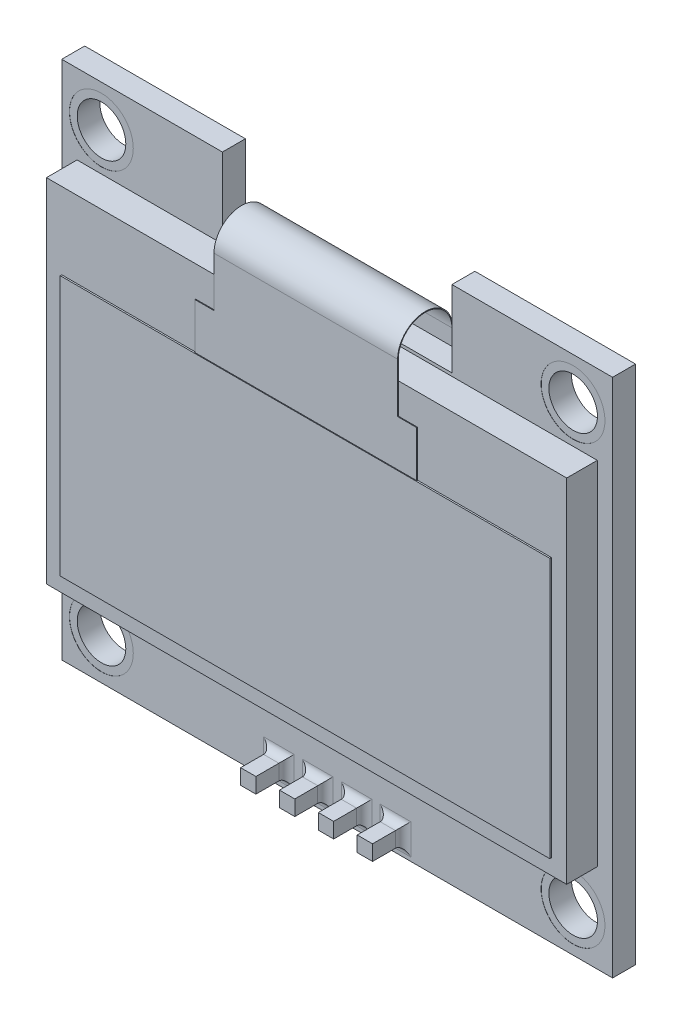
SolidWorks part; units mm, degrees
ref_plane "Alzado" through (0, 0, 0) normal (0, 0, 1) x (1, 0, 0)
ref_plane "Planta" through (0, 0, 0) normal (0, 1, 0) x (1, 0, 0)
ref_plane "Vista lateral" through (0, 0, 0) normal (1, 0, 0) x (0, 0, -1)
sketch "Croquis1" plane through (0, 0, 0) normal (0, 0, 1) x (1, 0, 0)
  line L1 (-18, 17) -> (18, 17)
  line L2 (-18, 17) -> (-18, -17)
  line L3 (-18, -17) -> (18, -17)
  line L4 (18, 17) -> (18, -17)
  line L5 (-18, 17) -> (18, -17) construction
  line L6 (-18, -17) -> (18, 17) construction
  point P0 (0, 0)
  dimension "D1" = 36
  dimension "D2" = 34
extrude "Saliente-Extruir1" add sketch "Croquis1" along normal blind 1.5
sketch "Croquis2" plane through (0, 0, 1.5) normal (0, 0, 1) x (1, 0, 0)
  line L0 (18, 17) -> (-18, 17) construction
  line L1 (-7.5, 17) -> (7.5, 17)
  line L2 (-7.5, 17) -> (-7.5, 12)
  line L3 (-7.5, 12) -> (7.5, 12)
  line L4 (7.5, 17) -> (7.5, 12)
  point P6 (0, 12)
  point P7 (0, 17)
  dimension "D1" = 15
  dimension "D2" = 5
extrude "Cortar-Extruir1" cut sketch "Croquis2" against normal blind 1.5
sketch "Croquis3" plane through (0, 0, 1.5) normal (0, 0, 1) x (1, 0, 0)
  line L0 (15.4125, 14.2875) -> (15.4125, -14.2875) construction
  line L1 (18, -17) -> (18, 17) construction
  line L2 (-15.4125, -14.2875) -> (15.4125, -14.2875) construction
  line L3 (-18, -17) -> (18, -17) construction
  circle A0 centre (-15.4125, 14.2875) radius 1.5875
  circle A1 centre (15.4125, 14.2875) radius 1.5875
  circle A2 centre (15.4125, -14.2875) radius 1.5875
  circle A3 centre (-15.4125, -14.2875) radius 1.5875
  point P8 (15.4125, 15.875)
  point P9 (17, 14.2875)
  point P10 (15.4125, -15.875)
  point P11 (-17, 14.2875)
  point P12 (15.4125, 0)
  point P13 (18, 0)
  point P14 (0, -14.2875)
  point P17 (0, -17)
  dimension "D1" = 3.175
  dimension "D2" = 31.75
  dimension "D3" = 34
extrude "Cortar-Extruir2" cut sketch "Croquis3" against normal blind 2.54
sketch "Croquis4" plane through (0, 0, 1.5) normal (0, 0, 1) x (1, 0, 0)
  line L0 (-18, -17) -> (18, -17) construction
  line L1 (-17, 11.8) -> (17, 11.8)
  line L2 (-17, 11.8) -> (-17, -11.2)
  line L3 (-17, -11.2) -> (17, -11.2)
  line L4 (17, 11.8) -> (17, -11.2)
  point P6 (0, -11.2)
  dimension "D1" = 34
  dimension "D2" = 23
  dimension "D3" = 5.8
extrude "Saliente-Extruir2" add sketch "Croquis4" along normal blind 2
sketch "Croquis5" plane through (0, 0, 3.5) normal (0, 0, 1) x (1, 0, 0)
  line L0 (-17, -11.2) -> (17, -11.2) construction
  line L1 (16, -10.2) -> (-16, -10.2)
  line L2 (16, -10.2) -> (16, 6.8)
  line L3 (16, 6.8) -> (-16, 6.8)
  line L4 (-16, -10.2) -> (-16, 6.8)
  line L5 (17, -11.2) -> (17, 11.8) construction
  line L6 (-17, 11.8) -> (-17, -11.2) construction
  line L7 (17, 11.8) -> (-17, 11.8) construction
  dimension "D1" = 1
  dimension "D2" = 1
  dimension "D3" = 1
  dimension "D4" = 5
sketch "Croquis7" plane through (0, 0, 0) normal (0, 0, -1) x (-1, 0, 0)
  line L0 (-11, 6) -> (11, 6)
  line L1 (-11, 6) -> (-11, 9)
  line L2 (-11, 9) -> (11, 9) construction
  line L3 (11, 9) -> (11, 6)
  line L4 (7.5, 12) -> (-7.5, 12) construction
  line L5 (-11, 9) -> (-6, 12.5)
  line L6 (-6, 12.5) -> (-6, 13)
  line L7 (-6, 13) -> (6, 13)
  line L8 (6, 13) -> (6, 12.5)
  line L9 (6, 12.5) -> (11, 9)
  point P3 (0, 6)
  point P7 (0, 13)
  dimension "D1" = 22
  dimension "D2" = 3
  dimension "D3" = 6
  dimension "D4" = 3.5
  dimension "D6" = 12
  dimension "D7" = 0.5
extrude "Saliente-Extruir3" add sketch "Croquis7" along normal blind 0.05
sketch "Croquis8" plane through (0, 0, 0) normal (1, 0, 0) x (0, 0, -1)
  line L0 (-3.5, 11.8) -> (-3.55, 11.8) construction
  line L1 (0.025, 13) -> (0.025, 13.0479)
  line L2 (0.05, 13) -> (0, 13) construction
  line L3 (-3.525, 13.0479) -> (-3.525, 11.8)
  arc A0 (0.025, 13.0479) -> (-3.525, 13.0479) centre (-1.75, 13.0479) ccw
  point P3 (-3.525, 11.8)
  dimension "D1" = 0.05
sketch "Croquis12" plane through (0, 13, 0) normal (0, 1, 0) x (1, 0, 0)
  line L1 (6, 0) -> (-6, 0)
  line L2 (6, 0) -> (6, 0.05)
  line L3 (6, 0.05) -> (-6, 0.05)
  line L4 (-6, 0) -> (-6, 0.05)
extrude "Saliente-Extruir5" add sketch "Croquis5" along normal blind 0.1
sketch "Croquis14" plane through (0, 0, 3.5) normal (0, 0, 1) x (1, 0, 0)
  line L0 (17, 11.8) -> (-17, 11.8) construction
  line L1 (16, 6.8) -> (-16, 6.8) construction
  line L2 (-6, 11.8) -> (6, 11.8)
  line L3 (-6, 11.8) -> (-6, 9.8)
  line L5 (6, 11.8) -> (6, 9.8)
  line L6 (-7.2481, 3.8) -> (7.2481, 3.8)
  line L7 (-7.2481, 3.8) -> (-7.2481, 9.8)
  line L8 (-7.2481, 9.8) -> (-6, 9.8)
  line L9 (7.2481, 3.8) -> (7.2481, 9.8)
  line L10 (-7.2481, 3.8) -> (7.2481, 9.8) construction
  line L11 (-7.2481, 9.8) -> (7.2481, 3.8) construction
  line L12 (16, 6.8) -> (-16, 6.8) construction
  line L13 (6, 9.8) -> (7.2481, 9.8)
  point P0 (-6, 11.8)
  point P1 (6, 11.8)
  point P8 (0, 6.8)
  dimension "D1" = 3
extrude "Saliente-Extruir6" add sketch "Croquis14" along normal blind 0.05
sweep "Barrer3" add profiles "Croquis12" path "Croquis8"
sketch "Croquis15" plane through (0, 0, 1.5) normal (0, 0, 1) x (1, 0, 0)
  line L0 (-18, -17) -> (18, -17) construction
  line L1 (1.77, -16.25) -> (0.77, -16.25)
  line L2 (4.31, -16.25) -> (3.31, -16.25)
  line L3 (4.31, -16.25) -> (4.31, -15.25)
  line L4 (4.31, -15.25) -> (3.31, -15.25)
  line L5 (3.31, -16.25) -> (3.31, -15.25)
  line L6 (4.31, -16.25) -> (3.31, -15.25) construction
  line L7 (4.31, -15.25) -> (3.31, -16.25) construction
  line L8 (1.77, -16.25) -> (1.77, -15.25)
  line L9 (1.77, -15.25) -> (0.77, -15.25)
  line L10 (0.77, -16.25) -> (0.77, -15.25)
  line L11 (1.77, -16.25) -> (0.77, -15.25) construction
  line L12 (1.77, -15.25) -> (0.77, -16.25) construction
  line L13 (-0.77, -16.25) -> (-1.77, -16.25)
  line L14 (-0.77, -16.25) -> (-0.77, -15.25)
  line L15 (-0.77, -15.25) -> (-1.77, -15.25)
  line L16 (-1.77, -16.25) -> (-1.77, -15.25)
  line L17 (-0.77, -16.25) -> (-1.77, -15.25) construction
  line L18 (-0.77, -15.25) -> (-1.77, -16.25) construction
  line L19 (-3.31, -16.25) -> (-4.31, -16.25)
  line L20 (-3.31, -16.25) -> (-3.31, -15.25)
  line L21 (-3.31, -15.25) -> (-4.31, -15.25)
  line L22 (-4.31, -16.25) -> (-4.31, -15.25)
  line L23 (-3.31, -16.25) -> (-4.31, -15.25) construction
  line L24 (-3.31, -15.25) -> (-4.31, -16.25) construction
  line L25 (3.81, -15.75) -> (1.27, -15.75) construction
  line L26 (0.77, -15.75) -> (-0.77, -15.75) construction
  point P0 (3.81, -15.75)
  point P3 (3.81, -15.75)
  point P10 (1.27, -15.75)
  point P11 (1.27, -15.75)
  point P16 (-1.27, -15.75)
  point P17 (-1.27, -15.75)
  point P22 (-3.81, -15.75)
  point P23 (-3.81, -15.75)
  point P30 (0, -15.75)
  dimension "D1" = 1.25
  dimension "D2" = 1
  dimension "D3" = 1
  dimension "D5" = 2.54
  dimension "D4" = 4
extrude "Saliente-Extruir7" add sketch "Croquis15" along normal blind 2 and the other way blind 10
sketch "Croquis16" plane through (0, 0, 0) normal (0, 0, -1) x (-1, 0, 0)
  line L0 (4.31, -15.25) -> (4.31, -16.25) construction
  line L1 (4.31, -16.25) -> (3.31, -16.25) construction
  line L2 (1.77, -16.25) -> (0.77, -16.25) construction
  line L3 (4.81, -14.75) -> (2.81, -14.75)
  line L4 (4.81, -14.75) -> (4.81, -16.75)
  line L5 (4.81, -16.75) -> (2.81, -16.75)
  line L6 (2.81, -14.75) -> (2.81, -16.75)
  line L7 (4.81, -14.75) -> (2.81, -16.75) construction
  line L8 (4.81, -16.75) -> (2.81, -14.75) construction
  line L9 (0.27, -16.75) -> (2.27, -16.75)
  line L10 (0.27, -16.75) -> (0.27, -14.75)
  line L11 (0.27, -14.75) -> (2.27, -14.75)
  line L12 (2.27, -16.75) -> (2.27, -14.75)
  line L13 (0.27, -16.75) -> (2.27, -14.75) construction
  line L14 (0.27, -14.75) -> (2.27, -16.75) construction
  line L15 (-2.27, -16.75) -> (-0.27, -16.75)
  line L16 (-2.27, -16.75) -> (-2.27, -14.75)
  line L17 (-2.27, -14.75) -> (-0.27, -14.75)
  line L18 (-0.27, -16.75) -> (-0.27, -14.75)
  line L19 (-2.27, -16.75) -> (-0.27, -14.75) construction
  line L20 (-2.27, -14.75) -> (-0.27, -16.75) construction
  line L21 (-4.81, -16.75) -> (-2.81, -16.75)
  line L22 (-4.81, -16.75) -> (-4.81, -14.75)
  line L23 (-4.81, -14.75) -> (-2.81, -14.75)
  line L24 (-2.81, -16.75) -> (-2.81, -14.75)
  line L25 (-4.81, -16.75) -> (-2.81, -14.75) construction
  line L26 (-4.81, -14.75) -> (-2.81, -16.75) construction
  line L27 (-0.77, -16.25) -> (-1.77, -16.25) construction
  line L28 (-3.31, -16.25) -> (-4.31, -16.25) construction
  point P0 (4.31, -15.75)
  point P1 (3.81, -16.25)
  point P4 (3.81, -15.75)
  point P7 (3.81, -15.75)
  point P12 (-1.27, -15.75)
  point P14 (1.27, -15.75)
  point P22 (-3.81, -15.75)
  point P27 (-1.27, -16.25)
  point P28 (-3.81, -16.25)
  point P30 (1.27, -16.25)
  dimension "D1" = 2
  dimension "D2" = 2
extrude "Saliente-Extruir8" add sketch "Croquis16" along normal blind 2
sketch "Croquis17" plane through (0, 0, 0) normal (0, 0, -1) x (-1, 0, 0)
  line L0 (4.81, -16.75) -> (4.81, -14.75) construction
  line L1 (4.81, -16.5) -> (-4.81, -16.5)
  line L2 (4.81, -16.5) -> (4.81, -15)
  line L3 (4.81, -15) -> (-4.81, -15)
  line L4 (-4.81, -16.5) -> (-4.81, -15)
  line L5 (-4.81, -14.75) -> (-4.81, -16.75) construction
  line L6 (-4.81, -14.75) -> (-4.81, -16.75) construction
  point P8 (-4.81, -15.75)
  dimension "D1" = 1.5
extrude "Saliente-Extruir9" add sketch "Croquis17" along normal blind 2
fillet "Redondeo1" radius 0.5 16 edges at (-3.31, -15.75, 1.5) (-3.81, -16.25, 1.5) (-4.31, -15.75, 1.5) (-3.81, -15.25, 1.5) (-0.77, -15.75, 1.5) (-1.27, -15.25, 1.5) (-1.77, -15.75, 1.5) (-1.27, -16.25, 1.5) (1.27, -16.25, 1.5) (0.77, -15.75, 1.5) (1.27, -15.25, 1.5) (1.77, -15.75, 1.5) (3.31, -15.75, 1.5) (3.81, -16.25, 1.5) (4.31, -15.75, 1.5) (3.81, -15.25, 1.5)
sketch "Croquis18" plane through (0, 0, 0) normal (0, 0, -1) x (-1, 0, 0)
  line L0 (0, 0) -> (3.6392, 0) construction
  line L1 (-10.7273, 6.7625) -> (-10.6273, 6.7625)
  line L2 (-10.7273, 6.7625) -> (-10.7273, 4.7625)
  line L3 (-10.7273, 4.7625) -> (-10.6273, 4.7625)
  line L4 (-10.6273, 6.7625) -> (-10.6273, 4.7625)
  line L5 (-10.4273, 6.7625) -> (-10.4273, 4.7625)
  line L6 (-10.3273, 6.7625) -> (-10.3273, 4.7625)
  line L7 (-10.4273, 4.7625) -> (-10.3273, 4.7625)
  line L8 (-10.4273, 6.7625) -> (-10.3273, 6.7625)
  line L9 (-10.1273, 6.7625) -> (-10.1273, 4.7625)
  line L10 (-10.0273, 6.7625) -> (-10.0273, 4.7625)
  line L11 (-10.1273, 4.7625) -> (-10.0273, 4.7625)
  line L12 (-10.1273, 6.7625) -> (-10.0273, 6.7625)
  line L13 (-9.8273, 6.7625) -> (-9.8273, 4.7625)
  line L14 (-9.7273, 6.7625) -> (-9.7273, 4.7625)
  line L15 (-9.8273, 4.7625) -> (-9.7273, 4.7625)
  line L16 (-9.8273, 6.7625) -> (-9.7273, 6.7625)
  line L17 (-9.5273, 6.7625) -> (-9.5273, 4.7625)
  line L18 (-9.4273, 6.7625) -> (-9.4273, 4.7625)
  line L19 (-9.5273, 4.7625) -> (-9.4273, 4.7625)
  line L20 (-9.5273, 6.7625) -> (-9.4273, 6.7625)
  line L21 (-9.2273, 6.7625) -> (-9.2273, 4.7625)
  line L22 (-9.1273, 6.7625) -> (-9.1273, 4.7625)
  line L23 (-9.2273, 4.7625) -> (-9.1273, 4.7625)
  line L24 (-9.2273, 6.7625) -> (-9.1273, 6.7625)
  line L25 (-8.9273, 6.7625) -> (-8.9273, 4.7625)
  line L26 (-8.8273, 6.7625) -> (-8.8273, 4.7625)
  line L27 (-8.9273, 4.7625) -> (-8.8273, 4.7625)
  line L28 (-8.9273, 6.7625) -> (-8.8273, 6.7625)
  line L29 (-8.6273, 6.7625) -> (-8.6273, 4.7625)
  line L30 (-8.5273, 6.7625) -> (-8.5273, 4.7625)
  line L31 (-8.6273, 4.7625) -> (-8.5273, 4.7625)
  line L32 (-8.6273, 6.7625) -> (-8.5273, 6.7625)
  line L33 (-8.3273, 6.7625) -> (-8.3273, 4.7625)
  line L34 (-8.2273, 6.7625) -> (-8.2273, 4.7625)
  line L35 (-8.3273, 4.7625) -> (-8.2273, 4.7625)
  line L36 (-8.3273, 6.7625) -> (-8.2273, 6.7625)
  line L37 (-8.0273, 6.7625) -> (-8.0273, 4.7625)
  line L38 (-7.9273, 6.7625) -> (-7.9273, 4.7625)
  line L39 (-8.0273, 4.7625) -> (-7.9273, 4.7625)
  line L40 (-8.0273, 6.7625) -> (-7.9273, 6.7625)
  line L41 (-7.7273, 6.7625) -> (-7.7273, 4.7625)
  line L42 (-7.6273, 6.7625) -> (-7.6273, 4.7625)
  line L43 (-7.7273, 4.7625) -> (-7.6273, 4.7625)
  line L44 (-7.7273, 6.7625) -> (-7.6273, 6.7625)
  line L45 (-7.4273, 6.7625) -> (-7.4273, 4.7625)
  line L46 (-7.3273, 6.7625) -> (-7.3273, 4.7625)
  line L47 (-7.4273, 4.7625) -> (-7.3273, 4.7625)
  line L48 (-7.4273, 6.7625) -> (-7.3273, 6.7625)
  line L49 (-7.1273, 6.7625) -> (-7.1273, 4.7625)
  line L50 (-7.0273, 6.7625) -> (-7.0273, 4.7625)
  line L51 (-7.1273, 4.7625) -> (-7.0273, 4.7625)
  line L52 (-7.1273, 6.7625) -> (-7.0273, 6.7625)
  line L53 (-6.8273, 6.7625) -> (-6.8273, 4.7625)
  line L54 (-6.7273, 6.7625) -> (-6.7273, 4.7625)
  line L55 (-6.8273, 4.7625) -> (-6.7273, 4.7625)
  line L56 (-6.8273, 6.7625) -> (-6.7273, 6.7625)
  line L57 (-6.5273, 6.7625) -> (-6.5273, 4.7625)
  line L58 (-6.4273, 6.7625) -> (-6.4273, 4.7625)
  line L59 (-6.5273, 4.7625) -> (-6.4273, 4.7625)
  line L60 (-6.5273, 6.7625) -> (-6.4273, 6.7625)
  line L61 (-6.2273, 6.7625) -> (-6.2273, 4.7625)
  line L62 (-6.1273, 6.7625) -> (-6.1273, 4.7625)
  line L63 (-6.2273, 4.7625) -> (-6.1273, 4.7625)
  line L64 (-6.2273, 6.7625) -> (-6.1273, 6.7625)
  line L65 (-5.9273, 6.7625) -> (-5.9273, 4.7625)
  line L66 (-5.8273, 6.7625) -> (-5.8273, 4.7625)
  line L67 (-5.9273, 4.7625) -> (-5.8273, 4.7625)
  line L68 (-5.9273, 6.7625) -> (-5.8273, 6.7625)
  line L69 (-5.6273, 6.7625) -> (-5.6273, 4.7625)
  line L70 (-5.5273, 6.7625) -> (-5.5273, 4.7625)
  line L71 (-5.6273, 4.7625) -> (-5.5273, 4.7625)
  line L72 (-5.6273, 6.7625) -> (-5.5273, 6.7625)
  line L73 (-5.3273, 6.7625) -> (-5.3273, 4.7625)
  line L74 (-5.2273, 6.7625) -> (-5.2273, 4.7625)
  line L75 (-5.3273, 4.7625) -> (-5.2273, 4.7625)
  line L76 (-5.3273, 6.7625) -> (-5.2273, 6.7625)
  line L77 (-5.0273, 6.7625) -> (-5.0273, 4.7625)
  line L78 (-4.9273, 6.7625) -> (-4.9273, 4.7625)
  line L79 (-5.0273, 4.7625) -> (-4.9273, 4.7625)
  line L80 (-5.0273, 6.7625) -> (-4.9273, 6.7625)
  line L81 (-4.7273, 6.7625) -> (-4.7273, 4.7625)
  line L82 (-4.6273, 6.7625) -> (-4.6273, 4.7625)
  line L83 (-4.7273, 4.7625) -> (-4.6273, 4.7625)
  line L84 (-4.7273, 6.7625) -> (-4.6273, 6.7625)
  line L85 (-4.4273, 6.7625) -> (-4.4273, 4.7625)
  line L86 (-4.3273, 6.7625) -> (-4.3273, 4.7625)
  line L87 (-4.4273, 4.7625) -> (-4.3273, 4.7625)
  line L88 (-4.4273, 6.7625) -> (-4.3273, 6.7625)
  line L89 (-4.1273, 6.7625) -> (-4.1273, 4.7625)
  line L90 (-4.0273, 6.7625) -> (-4.0273, 4.7625)
  line L91 (-4.1273, 4.7625) -> (-4.0273, 4.7625)
  line L92 (-4.1273, 6.7625) -> (-4.0273, 6.7625)
  line L93 (-3.8273, 6.7625) -> (-3.8273, 4.7625)
  line L94 (-3.7273, 6.7625) -> (-3.7273, 4.7625)
  line L95 (-3.8273, 4.7625) -> (-3.7273, 4.7625)
  line L96 (-3.8273, 6.7625) -> (-3.7273, 6.7625)
  line L97 (-3.5273, 6.7625) -> (-3.5273, 4.7625)
  line L98 (-3.4273, 6.7625) -> (-3.4273, 4.7625)
  line L99 (-3.5273, 4.7625) -> (-3.4273, 4.7625)
  line L100 (-3.5273, 6.7625) -> (-3.4273, 6.7625)
  line L101 (-3.2273, 6.7625) -> (-3.2273, 4.7625)
  line L102 (-3.1273, 6.7625) -> (-3.1273, 4.7625)
  line L103 (-3.2273, 4.7625) -> (-3.1273, 4.7625)
  line L104 (-3.2273, 6.7625) -> (-3.1273, 6.7625)
  line L105 (-2.9273, 6.7625) -> (-2.9273, 4.7625)
  line L106 (-2.8273, 6.7625) -> (-2.8273, 4.7625)
  line L107 (-2.9273, 4.7625) -> (-2.8273, 4.7625)
  line L108 (-2.9273, 6.7625) -> (-2.8273, 6.7625)
  line L109 (-2.6273, 6.7625) -> (-2.6273, 4.7625)
  line L110 (-2.5273, 6.7625) -> (-2.5273, 4.7625)
  line L111 (-2.6273, 4.7625) -> (-2.5273, 4.7625)
  line L112 (-2.6273, 6.7625) -> (-2.5273, 6.7625)
  line L113 (-2.3273, 6.7625) -> (-2.3273, 4.7625)
  line L114 (-2.2273, 6.7625) -> (-2.2273, 4.7625)
  line L115 (-2.3273, 4.7625) -> (-2.2273, 4.7625)
  line L116 (-2.3273, 6.7625) -> (-2.2273, 6.7625)
  line L117 (-2.0273, 6.7625) -> (-2.0273, 4.7625)
  line L118 (-1.9273, 6.7625) -> (-1.9273, 4.7625)
  line L119 (-2.0273, 4.7625) -> (-1.9273, 4.7625)
  line L120 (-2.0273, 6.7625) -> (-1.9273, 6.7625)
  line L121 (-1.7273, 6.7625) -> (-1.7273, 4.7625)
  line L122 (-1.6273, 6.7625) -> (-1.6273, 4.7625)
  line L123 (-1.7273, 4.7625) -> (-1.6273, 4.7625)
  line L124 (-1.7273, 6.7625) -> (-1.6273, 6.7625)
  line L125 (-1.4273, 6.7625) -> (-1.4273, 4.7625)
  line L126 (-1.3273, 6.7625) -> (-1.3273, 4.7625)
  line L127 (-1.4273, 4.7625) -> (-1.3273, 4.7625)
  line L128 (-1.4273, 6.7625) -> (-1.3273, 6.7625)
  line L129 (-1.1273, 6.7625) -> (-1.1273, 4.7625)
  line L130 (-1.0273, 6.7625) -> (-1.0273, 4.7625)
  line L131 (-1.1273, 4.7625) -> (-1.0273, 4.7625)
  line L132 (-1.1273, 6.7625) -> (-1.0273, 6.7625)
  line L133 (-0.8273, 6.7625) -> (-0.8273, 4.7625)
  line L134 (-0.7273, 6.7625) -> (-0.7273, 4.7625)
  line L135 (-0.8273, 4.7625) -> (-0.7273, 4.7625)
  line L136 (-0.8273, 6.7625) -> (-0.7273, 6.7625)
  line L137 (-0.5273, 6.7625) -> (-0.5273, 4.7625)
  line L138 (-0.4273, 6.7625) -> (-0.4273, 4.7625)
  line L139 (-0.5273, 4.7625) -> (-0.4273, 4.7625)
  line L140 (-0.5273, 6.7625) -> (-0.4273, 6.7625)
  line L141 (-0.2273, 6.7625) -> (-0.2273, 4.7625)
  line L142 (-0.1273, 6.7625) -> (-0.1273, 4.7625)
  line L143 (-0.2273, 4.7625) -> (-0.1273, 4.7625)
  line L144 (-0.2273, 6.7625) -> (-0.1273, 6.7625)
  line L145 (0.0727, 6.7625) -> (0.0727, 4.7625)
  line L146 (0.1727, 6.7625) -> (0.1727, 4.7625)
  line L147 (0.0727, 4.7625) -> (0.1727, 4.7625)
  line L148 (0.0727, 6.7625) -> (0.1727, 6.7625)
  line L149 (0.3727, 6.7625) -> (0.3727, 4.7625)
  line L150 (0.4727, 6.7625) -> (0.4727, 4.7625)
  line L151 (0.3727, 4.7625) -> (0.4727, 4.7625)
  line L152 (0.3727, 6.7625) -> (0.4727, 6.7625)
  line L153 (0.6727, 6.7625) -> (0.6727, 4.7625)
  line L154 (0.7727, 6.7625) -> (0.7727, 4.7625)
  line L155 (0.6727, 4.7625) -> (0.7727, 4.7625)
  line L156 (0.6727, 6.7625) -> (0.7727, 6.7625)
  line L157 (0.9727, 6.7625) -> (0.9727, 4.7625)
  line L158 (1.0727, 6.7625) -> (1.0727, 4.7625)
  line L159 (0.9727, 4.7625) -> (1.0727, 4.7625)
  line L160 (0.9727, 6.7625) -> (1.0727, 6.7625)
  line L161 (1.2727, 6.7625) -> (1.2727, 4.7625)
  line L162 (1.3727, 6.7625) -> (1.3727, 4.7625)
  line L163 (1.2727, 4.7625) -> (1.3727, 4.7625)
  line L164 (1.2727, 6.7625) -> (1.3727, 6.7625)
  line L165 (1.5727, 6.7625) -> (1.5727, 4.7625)
  line L166 (1.6727, 6.7625) -> (1.6727, 4.7625)
  line L167 (1.5727, 4.7625) -> (1.6727, 4.7625)
  line L168 (1.5727, 6.7625) -> (1.6727, 6.7625)
  line L169 (1.8727, 6.7625) -> (1.8727, 4.7625)
  line L170 (1.9727, 6.7625) -> (1.9727, 4.7625)
  line L171 (1.8727, 4.7625) -> (1.9727, 4.7625)
  line L172 (1.8727, 6.7625) -> (1.9727, 6.7625)
  line L173 (2.1727, 6.7625) -> (2.1727, 4.7625)
  line L174 (2.2727, 6.7625) -> (2.2727, 4.7625)
  line L175 (2.1727, 4.7625) -> (2.2727, 4.7625)
  line L176 (2.1727, 6.7625) -> (2.2727, 6.7625)
  line L177 (2.4727, 6.7625) -> (2.4727, 4.7625)
  line L178 (2.5727, 6.7625) -> (2.5727, 4.7625)
  line L179 (2.4727, 4.7625) -> (2.5727, 4.7625)
  line L180 (2.4727, 6.7625) -> (2.5727, 6.7625)
  line L181 (2.7727, 6.7625) -> (2.7727, 4.7625)
  line L182 (2.8727, 6.7625) -> (2.8727, 4.7625)
  line L183 (2.7727, 4.7625) -> (2.8727, 4.7625)
  line L184 (2.7727, 6.7625) -> (2.8727, 6.7625)
  line L185 (3.0727, 6.7625) -> (3.0727, 4.7625)
  line L186 (3.1727, 6.7625) -> (3.1727, 4.7625)
  line L187 (3.0727, 4.7625) -> (3.1727, 4.7625)
  line L188 (3.0727, 6.7625) -> (3.1727, 6.7625)
  line L189 (3.3727, 6.7625) -> (3.3727, 4.7625)
  line L190 (3.4727, 6.7625) -> (3.4727, 4.7625)
  line L191 (3.3727, 4.7625) -> (3.4727, 4.7625)
  line L192 (3.3727, 6.7625) -> (3.4727, 6.7625)
  line L193 (3.6727, 6.7625) -> (3.6727, 4.7625)
  line L194 (3.7727, 6.7625) -> (3.7727, 4.7625)
  line L195 (3.6727, 4.7625) -> (3.7727, 4.7625)
  line L196 (3.6727, 6.7625) -> (3.7727, 6.7625)
  line L197 (3.9727, 6.7625) -> (3.9727, 4.7625)
  line L198 (4.0727, 6.7625) -> (4.0727, 4.7625)
  line L199 (3.9727, 4.7625) -> (4.0727, 4.7625)
  line L200 (3.9727, 6.7625) -> (4.0727, 6.7625)
  line L201 (4.2727, 6.7625) -> (4.2727, 4.7625)
  line L202 (4.3727, 6.7625) -> (4.3727, 4.7625)
  line L203 (4.2727, 4.7625) -> (4.3727, 4.7625)
  line L204 (4.2727, 6.7625) -> (4.3727, 6.7625)
  line L205 (4.5727, 6.7625) -> (4.5727, 4.7625)
  line L206 (4.6727, 6.7625) -> (4.6727, 4.7625)
  line L207 (4.5727, 4.7625) -> (4.6727, 4.7625)
  line L208 (4.5727, 6.7625) -> (4.6727, 6.7625)
  line L209 (4.8727, 6.7625) -> (4.8727, 4.7625)
  line L210 (4.9727, 6.7625) -> (4.9727, 4.7625)
  line L211 (4.8727, 4.7625) -> (4.9727, 4.7625)
  line L212 (4.8727, 6.7625) -> (4.9727, 6.7625)
  line L213 (5.1727, 6.7625) -> (5.1727, 4.7625)
  line L214 (5.2727, 6.7625) -> (5.2727, 4.7625)
  line L215 (5.1727, 4.7625) -> (5.2727, 4.7625)
  line L216 (5.1727, 6.7625) -> (5.2727, 6.7625)
  line L217 (5.4727, 6.7625) -> (5.4727, 4.7625)
  line L218 (5.5727, 6.7625) -> (5.5727, 4.7625)
  line L219 (5.4727, 4.7625) -> (5.5727, 4.7625)
  line L220 (5.4727, 6.7625) -> (5.5727, 6.7625)
  line L221 (5.7727, 6.7625) -> (5.7727, 4.7625)
  line L222 (5.8727, 6.7625) -> (5.8727, 4.7625)
  line L223 (5.7727, 4.7625) -> (5.8727, 4.7625)
  line L224 (5.7727, 6.7625) -> (5.8727, 6.7625)
  line L225 (6.0727, 6.7625) -> (6.0727, 4.7625)
  line L226 (6.1727, 6.7625) -> (6.1727, 4.7625)
  line L227 (6.0727, 4.7625) -> (6.1727, 4.7625)
  line L228 (6.0727, 6.7625) -> (6.1727, 6.7625)
  line L229 (6.3727, 6.7625) -> (6.3727, 4.7625)
  line L230 (6.4727, 6.7625) -> (6.4727, 4.7625)
  line L231 (6.3727, 4.7625) -> (6.4727, 4.7625)
  line L232 (6.3727, 6.7625) -> (6.4727, 6.7625)
  line L233 (6.6727, 6.7625) -> (6.6727, 4.7625)
  line L234 (6.7727, 6.7625) -> (6.7727, 4.7625)
  line L235 (6.6727, 4.7625) -> (6.7727, 4.7625)
  line L236 (6.6727, 6.7625) -> (6.7727, 6.7625)
  line L237 (6.9727, 6.7625) -> (6.9727, 4.7625)
  line L238 (7.0727, 6.7625) -> (7.0727, 4.7625)
  line L239 (6.9727, 4.7625) -> (7.0727, 4.7625)
  line L240 (6.9727, 6.7625) -> (7.0727, 6.7625)
  line L241 (7.2727, 6.7625) -> (7.2727, 4.7625)
  line L242 (7.3727, 6.7625) -> (7.3727, 4.7625)
  line L243 (7.2727, 4.7625) -> (7.3727, 4.7625)
  line L244 (7.2727, 6.7625) -> (7.3727, 6.7625)
  line L245 (7.5727, 6.7625) -> (7.5727, 4.7625)
  line L246 (7.6727, 6.7625) -> (7.6727, 4.7625)
  line L247 (7.5727, 4.7625) -> (7.6727, 4.7625)
  line L248 (7.5727, 6.7625) -> (7.6727, 6.7625)
  line L249 (7.8727, 6.7625) -> (7.8727, 4.7625)
  line L250 (7.9727, 6.7625) -> (7.9727, 4.7625)
  line L251 (7.8727, 4.7625) -> (7.9727, 4.7625)
  line L252 (7.8727, 6.7625) -> (7.9727, 6.7625)
  line L253 (8.1727, 6.7625) -> (8.1727, 4.7625)
  line L254 (8.2727, 6.7625) -> (8.2727, 4.7625)
  line L255 (8.1727, 4.7625) -> (8.2727, 4.7625)
  line L256 (8.1727, 6.7625) -> (8.2727, 6.7625)
  line L257 (8.4727, 6.7625) -> (8.4727, 4.7625)
  line L258 (8.5727, 6.7625) -> (8.5727, 4.7625)
  line L259 (8.4727, 4.7625) -> (8.5727, 4.7625)
  line L260 (8.4727, 6.7625) -> (8.5727, 6.7625)
  line L261 (8.7727, 6.7625) -> (8.7727, 4.7625)
  line L262 (8.8727, 6.7625) -> (8.8727, 4.7625)
  line L263 (8.7727, 4.7625) -> (8.8727, 4.7625)
  line L264 (8.7727, 6.7625) -> (8.8727, 6.7625)
  line L265 (9.0727, 6.7625) -> (9.0727, 4.7625)
  line L266 (9.1727, 6.7625) -> (9.1727, 4.7625)
  line L267 (9.0727, 4.7625) -> (9.1727, 4.7625)
  line L268 (9.0727, 6.7625) -> (9.1727, 6.7625)
  line L269 (9.3727, 6.7625) -> (9.3727, 4.7625)
  line L270 (9.4727, 6.7625) -> (9.4727, 4.7625)
  line L271 (9.3727, 4.7625) -> (9.4727, 4.7625)
  line L272 (9.3727, 6.7625) -> (9.4727, 6.7625)
  line L273 (9.6727, 6.7625) -> (9.6727, 4.7625)
  line L274 (9.7727, 6.7625) -> (9.7727, 4.7625)
  line L275 (9.6727, 4.7625) -> (9.7727, 4.7625)
  line L276 (9.6727, 6.7625) -> (9.7727, 6.7625)
  line L277 (9.9727, 6.7625) -> (9.9727, 4.7625)
  line L278 (10.0727, 6.7625) -> (10.0727, 4.7625)
  line L279 (9.9727, 4.7625) -> (10.0727, 4.7625)
  line L280 (9.9727, 6.7625) -> (10.0727, 6.7625)
  line L281 (10.2727, 6.7625) -> (10.2727, 4.7625)
  line L282 (10.3727, 6.7625) -> (10.3727, 4.7625)
  line L283 (10.2727, 4.7625) -> (10.3727, 4.7625)
  line L284 (10.2727, 6.7625) -> (10.3727, 6.7625)
  line L285 (10.5727, 6.7625) -> (10.5727, 4.7625)
  line L286 (10.6727, 6.7625) -> (10.6727, 4.7625)
  line L287 (10.5727, 4.7625) -> (10.6727, 4.7625)
  line L288 (10.5727, 6.7625) -> (10.6727, 6.7625)
  line L289 (-10.7273, 6.7625) -> (-10.4273, 6.7625) construction
  dimension "D1" = 0.1
  dimension "D2" = 2
  dimension "D4" = 0.3
  dimension "D3" = 72
extrude "Saliente-Extruir10" add sketch "Croquis18" along normal blind 0.1
sketch "Croquis19" plane through (0, 0, 0) normal (0, 0, -1) x (-1, 0, 0)
  line L0 (-18, -17) -> (-18, 17) construction
  line L1 (-13, 1) -> (-12.2, 1)
  line L2 (-13, 1) -> (-13, -1)
  line L3 (-13, -1) -> (-12.2, -1)
  line L4 (-12.2, 1) -> (-12.2, -1)
  line L5 (-13, 1) -> (-12.2, -1) construction
  line L6 (-13, -1) -> (-12.2, 1) construction
  line L7 (-18, 17) -> (-7.5, 17) construction
  point P0 (-12.6, 0)
  dimension "D1" = 0.8
  dimension "D2" = 2
  dimension "D3" = 5
  dimension "D4" = 18
extrude "Saliente-Extruir11" add sketch "Croquis19" along normal blind 1
sketch "Croquis20" plane through (0, -1, 0) normal (0, -1, 0) x (1, 0, 0)
  line L0 (13, 0) -> (12.2, 0) construction
  line L1 (12.6, -0.3596) -> (12.6, 0.3596) construction
  line L2 (12.6, -0.3596) -> (12.6, 0.3596)
  arc A0 (12.6, 0.3596) -> (12.6, -0.3596) centre (12.6, 0) ccw
revolve "Revolución1" add sketch "Croquis20" angle 360 about L1
sketch "Croquis21" plane through (0, 1, 0) normal (0, 1, 0) x (1, 0, 0)
  line L0 (12.2, 0) -> (13, 0) construction
  line L1 (12.6, 0.368) -> (12.6, -0.368)
  arc A0 (12.6, -0.368) -> (12.6, 0.368) centre (12.6, 0) ccw
revolve "Revolución2" add sketch "Croquis21" angle 360 about L1
pattern_linear "MatrizL1" count 11 spacing 2.8 along (-1, 0, 0) of "Revolución1", "Revolución2", "Saliente-Extruir11"
sketch "Croquis22" plane through (0, 0, 0) normal (0, 0, -1) x (-1, 0, 0)
  line L0 (-18, -17) -> (-18, 17) construction
  line L1 (-8, -6.0862) -> (-6, -6.0862)
  line L2 (-8, -6.0862) -> (-8, -5.2862)
  line L3 (-8, -5.2862) -> (-6, -5.2862)
  line L4 (-6, -6.0862) -> (-6, -5.2862)
  line L5 (-8, -6.0862) -> (-6, -5.2862) construction
  line L6 (-8, -5.2862) -> (-6, -6.0862) construction
  line L7 (-8, -8.3862) -> (-6, -8.3862)
  line L8 (-8, -8.3862) -> (-8, -7.5862)
  line L9 (-8, -7.5862) -> (-6, -7.5862)
  line L10 (-6, -8.3862) -> (-6, -7.5862)
  line L11 (-8, -8.3862) -> (-6, -7.5862) construction
  line L12 (-8, -7.5862) -> (-6, -8.3862) construction
  line L13 (-7, -7.5862) -> (-7, -6.0862) construction
  line L14 (-13, -1) -> (-12.2, -1) construction
  line L15 (0, 0) -> (0, -10.1593) construction
  line L16 (-13.35, -8.3362) -> (-11.85, -8.3362)
  line L17 (-13.35, -8.3362) -> (-13.35, -5.3362)
  line L18 (-13.35, -5.3362) -> (-11.85, -5.3362)
  line L19 (-11.85, -8.3362) -> (-11.85, -5.3362)
  line L20 (-13.35, -8.3362) -> (-11.85, -5.3362) construction
  line L21 (-13.35, -5.3362) -> (-11.85, -8.3362) construction
  line L22 (7, -7.5862) -> (7, -6.0862) construction
  line L23 (8, -7.5862) -> (6, -8.3862) construction
  line L24 (8, -8.3862) -> (6, -7.5862) construction
  line L25 (8, -5.2862) -> (6, -6.0862) construction
  line L26 (8, -6.0862) -> (6, -5.2862) construction
  line L27 (6, -8.3862) -> (6, -7.5862)
  line L28 (8, -7.5862) -> (6, -7.5862)
  line L29 (8, -8.3862) -> (8, -7.5862)
  line L30 (8, -8.3862) -> (6, -8.3862)
  line L31 (6, -6.0862) -> (6, -5.2862)
  line L32 (8, -5.2862) -> (6, -5.2862)
  line L33 (8, -6.0862) -> (8, -5.2862)
  line L34 (8, -6.0862) -> (6, -6.0862)
  line L36 (-14.36, -10.4142) -> (-12.36, -10.4142)
  line L37 (-14.36, -10.4142) -> (-14.36, -9.6142)
  line L38 (-14.36, -9.6142) -> (-12.36, -9.6142)
  line L39 (-12.36, -10.4142) -> (-12.36, -9.6142)
  line L40 (-14.36, -10.4142) -> (-12.36, -9.6142) construction
  line L41 (-14.36, -9.6142) -> (-12.36, -10.4142) construction
  line L48 (-2.2525, -13.3425) -> (-0.2525, -13.3425)
  line L49 (-2.2525, -13.3425) -> (-2.2525, -12.5425)
  line L50 (-2.2525, -12.5425) -> (-0.2525, -12.5425)
  line L51 (-0.2525, -13.3425) -> (-0.2525, -12.5425)
  line L52 (-2.2525, -13.3425) -> (-0.2525, -12.5425) construction
  line L53 (-2.2525, -12.5425) -> (-0.2525, -13.3425) construction
  line L55 (2.2525, -11.2669) -> (0.2525, -12.0669) construction
  line L56 (2.2525, -12.0669) -> (0.2525, -11.2669) construction
  line L61 (0.2525, -12.0669) -> (0.2525, -11.2669)
  line L62 (2.2525, -11.2669) -> (0.2525, -11.2669)
  line L63 (2.2525, -12.0669) -> (2.2525, -11.2669)
  line L64 (2.2525, -12.0669) -> (0.2525, -12.0669)
  point P0 (-7, -5.6862)
  point P5 (-7, -7.9862)
  point P14 (-7, -6.8362)
  point P15 (-12.6, -1)
  point P16 (-12.6, -6.8362)
  point P36 (7, -6.8362)
  point P37 (7, -7.9862)
  point P38 (7, -5.6862)
  point P39 (-13.36, -10.0142)
  point P44 (-1.2525, -12.9425)
  point P45 (-1.2525, -11.6669)
  point P71 (1.2525, -11.6669)
  point P72 (1.2525, -12.9425)
  dimension "D1" = 12
  dimension "D2" = 2
  dimension "D3" = 0.8
  dimension "D4" = 1.5
  dimension "D5" = 1.5
  dimension "D6" = 3
  dimension "D7" = 2
  dimension "D8" = 0.8
extrude "Saliente-Extruir12" add sketch "Croquis22" along normal blind 1
sketch "Croquis26" plane through (-8, 0, 0) normal (-1, 0, 0) x (0, 0, 1)
  line L0 (0, -8.3862) -> (0, -7.5862) construction
  line L2 (0.3716, -7.9862) -> (-0.3716, -7.9862)
  arc A0 (0.3716, -7.9862) -> (-0.3716, -7.9862) centre (0, -7.9862) ccw
revolve "Revolución4" add sketch "Croquis26" angle 360 about L2
sketch "Croquis27" plane through (-8, 0, 0) normal (-1, 0, 0) x (0, 0, 1)
  line L0 (0, -6.0862) -> (0, -5.2862) construction
  line L1 (-0.3621, -5.6862) -> (0.3621, -5.6862)
  arc A0 (0.3621, -5.6862) -> (-0.3621, -5.6862) centre (0, -5.6862) ccw
revolve "Revolución5" add sketch "Croquis27" angle 360 about L1
sketch "Croquis28" plane through (-6, 0, 0) normal (1, 0, 0) x (0, 0, -1)
  line L0 (0, -5.2862) -> (0, -6.0862) construction
  line L1 (0.3611, -5.6862) -> (-0.3611, -5.6862)
  arc A0 (-0.3611, -5.6862) -> (0.3611, -5.6862) centre (0, -5.6862) ccw
revolve "Revolución6" add sketch "Croquis28" angle 360 about L1
sketch "Croquis29" plane through (-6, 0, 0) normal (1, 0, 0) x (0, 0, -1)
  line L0 (0, -7.5862) -> (0, -8.3862) construction
  line L1 (0.3585, -7.9862) -> (-0.3585, -7.9862)
  arc A0 (-0.3585, -7.9862) -> (0.3585, -7.9862) centre (0, -7.9862) ccw
revolve "Revolución7" add sketch "Croquis29" angle 360 about L1
sketch "Croquis30" plane through (8, 0, 0) normal (1, 0, 0) x (0, 0, -1)
  line L0 (0, -5.2862) -> (0, -6.0862) construction
  line L1 (0.3473, -5.6862) -> (-0.3473, -5.6862)
  arc A0 (-0.3473, -5.6862) -> (0.3473, -5.6862) centre (0, -5.6862) ccw
revolve "Revolución8" add sketch "Croquis30" angle 360 about L1
sketch "Croquis31" plane through (8, 0, 0) normal (1, 0, 0) x (0, 0, -1)
  line L0 (0, -7.5862) -> (0, -8.3862) construction
  line L1 (0.349, -7.9862) -> (-0.349, -7.9862)
  arc A0 (-0.349, -7.9862) -> (0.349, -7.9862) centre (0, -7.9862) ccw
revolve "Revolución9" add sketch "Croquis31" angle 360 about L1
sketch "Croquis32" plane through (6, 0, 0) normal (-1, 0, 0) x (0, 0, 1)
  line L0 (0, -8.3862) -> (0, -7.5862) construction
  line L1 (0.3307, -7.9862) -> (-0.3307, -7.9862)
  arc A0 (0.3307, -7.9862) -> (-0.3307, -7.9862) centre (0, -7.9862) ccw
revolve "Revolución10" add sketch "Croquis32" angle 360 about L1
sketch "Croquis33" plane through (6, 0, 0) normal (-1, 0, 0) x (0, 0, 1)
  line L0 (0, -6.0862) -> (0, -5.2862) construction
  line L1 (0.3325, -5.6862) -> (-0.3325, -5.6862)
  arc A0 (0.3325, -5.6862) -> (-0.3325, -5.6862) centre (0, -5.6862) ccw
revolve "Revolución11" add sketch "Croquis33" angle 360 about L1
sketch "Croquis34" plane through (12.36, 0, 0) normal (-1, 0, 0) x (0, 0, 1)
  line L0 (0, -10.4142) -> (0, -9.6142) construction
  line L1 (0.3355, -10.0142) -> (-0.3355, -10.0142)
  arc A0 (0.3355, -10.0142) -> (-0.3355, -10.0142) centre (0, -10.0142) ccw
revolve "Revolución12" add sketch "Croquis34" angle 360 about L1
sketch "Croquis35" plane through (14.36, 0, 0) normal (1, 0, 0) x (0, 0, -1)
  line L0 (0, -9.6142) -> (0, -10.4142) construction
  line L1 (0.3483, -10.0142) -> (-0.3483, -10.0142)
  arc A0 (-0.3483, -10.0142) -> (0.3483, -10.0142) centre (0, -10.0142) ccw
revolve "Revolución13" add sketch "Croquis35" angle 360 about L1
sketch "Croquis36" plane through (2.2525, 0, 0) normal (1, 0, 0) x (0, 0, -1)
  line L0 (0, -12.5425) -> (0, -13.3425) construction
  line L1 (-0.3378, -12.9425) -> (0.3378, -12.9425)
  arc A0 (-0.3378, -12.9425) -> (0.3378, -12.9425) centre (0, -12.9425) ccw
revolve "Revolución14" add sketch "Croquis36" angle 360 about L1
sketch "Croquis37" plane through (-0.2525, 0, 0) normal (1, 0, 0) x (0, 0, -1)
  line L0 (0, -11.2669) -> (0, -12.0669) construction
  line L1 (-0.3496, -11.6669) -> (0.3496, -11.6669)
  arc A0 (-0.3496, -11.6669) -> (0.3496, -11.6669) centre (0, -11.6669) ccw
revolve "Revolución15" add sketch "Croquis37" angle 360 about L1
sketch "Croquis38" plane through (-2.2525, 0, 0) normal (-1, 0, 0) x (0, 0, 1)
  line L0 (0, -12.0669) -> (0, -11.2669) construction
  line L1 (0.3207, -11.6669) -> (-0.3207, -11.6669)
  arc A0 (0.3207, -11.6669) -> (-0.3207, -11.6669) centre (0, -11.6669) ccw
revolve "Revolución16" add sketch "Croquis38" angle 360 about L1
sketch "Croquis39" plane through (0.2525, 0, 0) normal (-1, 0, 0) x (0, 0, 1)
  line L0 (0, -13.3425) -> (0, -12.5425) construction
  line L1 (0.3351, -12.9425) -> (-0.3351, -12.9425)
  arc A0 (0.3351, -12.9425) -> (-0.3351, -12.9425) centre (0, -12.9425) ccw
revolve "Revolución17" add sketch "Croquis39" angle 360 about L1
sketch "Croquis40" plane through (0, 0, 0) normal (0, 0, -1) x (-1, 0, 0)
  line L0 (-13.35, -5.3362) -> (-13.35, -8.3362) construction
  line L1 (-11.85, -8.3362) -> (-11.85, -5.3362) construction
  line L2 (-13.35, -6.5916) -> (-14.2992, -6.5916)
  line L3 (-13.35, -6.5916) -> (-13.35, -7.0807)
  line L4 (-13.35, -7.0807) -> (-14.2992, -7.0807)
  line L5 (-14.2992, -6.5916) -> (-14.2992, -7.0807)
  line L6 (-11.85, -5.705) -> (-10.7863, -5.705)
  line L7 (-11.85, -5.705) -> (-11.85, -6.1941)
  line L8 (-11.85, -6.1941) -> (-10.7863, -6.1941)
  line L9 (-10.7863, -5.705) -> (-10.7863, -6.1941)
  line L10 (-11.85, -8.3362) -> (-11.85, -5.3362) construction
  line L11 (-11.85, -7.6014) -> (-10.7863, -7.6014)
  line L12 (-11.85, -7.6014) -> (-11.85, -8.0905)
  line L13 (-11.85, -8.0905) -> (-10.7863, -8.0905)
  line L14 (-10.7863, -7.6014) -> (-10.7863, -8.0905)
  point P0 (-13.35, -6.8362)
  point P7 (-14.2992, -6.8362)
extrude "Saliente-Extruir13" add sketch "Croquis40" along normal blind 0.5
fillet "Redondeo3" radius 1 3 edges at (14.2992, -6.8362, -0.5) (10.7863, -5.9495, -0.5) (10.7863, -7.8459, -0.5)
sketch "Croquis41" plane through (0, 0, 1.5) normal (0, 0, 1) x (1, 0, 0)
  line L0 (-15.4125, 12.2) -> (-15.4125, 12.7) construction
  circle A0 centre (-15.4125, 14.2875) radius 2.0875
  circle A1 centre (15.4125, 14.2875) radius 2.0875
  circle A2 centre (15.4125, -14.2875) radius 2.0875
  circle A3 centre (-15.4125, -14.2875) radius 2.0875
  circle A4 centre (-15.4125, 14.2875) radius 1.5875 construction
  dimension "D1" = 0.5
extrude "Cortar-Extruir4" cut sketch "Croquis41" against normal blind 0.01
sketch "Croquis42" plane through (0, 0, 0) normal (0, 0, -1) x (-1, 0, 0)
  line L0 (-15.4125, 12.2) -> (-15.4125, 12.7) construction
  circle A0 centre (-15.4125, 14.2875) radius 2.0875
  circle A1 centre (15.4125, 14.2875) radius 2.0875
  circle A2 centre (15.4125, -14.2875) radius 2.0875
  circle A3 centre (-15.4125, -14.2875) radius 2.0875
  circle A4 centre (-15.4125, 14.2875) radius 1.5875 construction
  dimension "D1" = 0.5
extrude "Cortar-Extruir5" cut sketch "Croquis42" against normal blind 0.01
